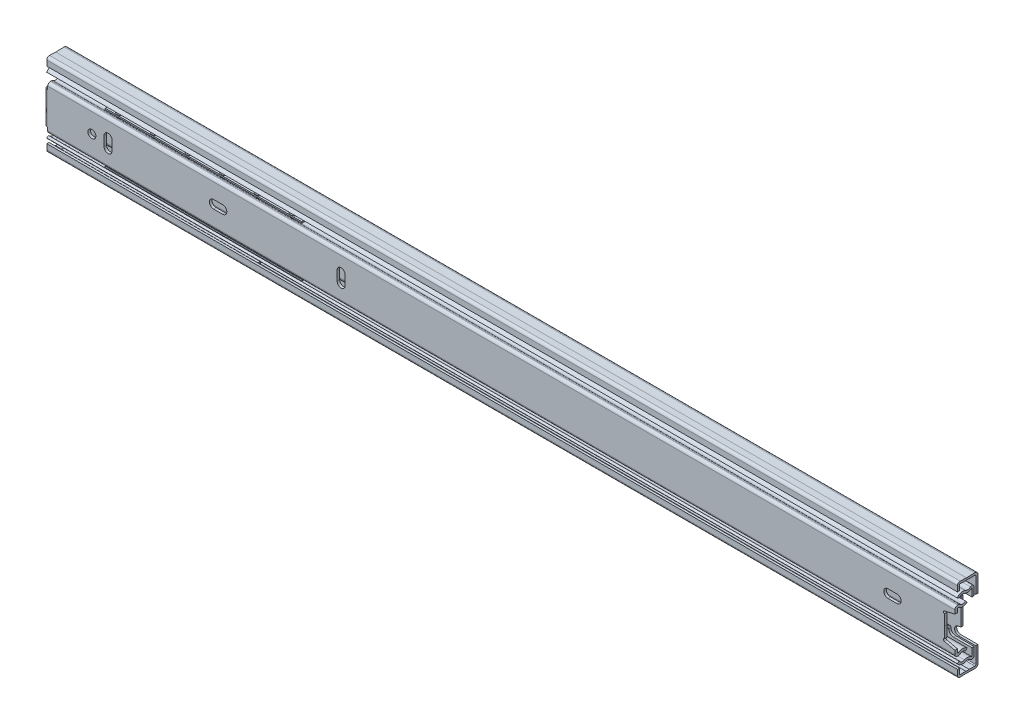
SolidWorks part; units mm, degrees
ref_plane "Front" through (0, 0, 0) normal (0, 0, 1) x (1, 0, 0)
ref_plane "Top" through (0, 0, 0) normal (0, 1, 0) x (1, 0, 0)
ref_plane "Right" through (0, 0, 0) normal (1, 0, 0) x (0, 0, -1)
sketch "Sketch1" plane through (0, 0, 0) normal (1, 0, 0) x (0, 0, -1)
  line L1 (5.6388, 0) -> (-5.6388, 0) construction
  line L4 (-4.1393, 22.8203) -> (-0.7433, 22.6989)
  line L5 (-1.1312, 21.5182) -> (-4.1819, 21.6273)
  line L6 (-4.445, 18.415) -> (-5.6388, 18.415)
  line L7 (-4.445, 21.3734) -> (-4.445, 18.415)
  line L8 (-5.6388, 18.415) -> (-5.6388, 21.3734)
  line L9 (3.9237, 21.6269) -> (0.7619, 21.5441)
  line L10 (5.6388, 0) -> (5.6388, 21.1191)
  line L11 (4.445, 21.1191) -> (4.445, 0)
  line L12 (5.6388, 0) -> (4.445, 0)
  line L13 (-0.7433, 22.6989) -> (3.8925, 22.8203)
  arc A0 (-4.445, 21.3734) -> (-4.1819, 21.6273) centre (-4.191, 21.3734) cw
  arc A1 (-5.6388, 21.3734) -> (-4.1393, 22.8203) centre (-4.191, 21.3734) cw
  arc A3 (3.9237, 21.6269) -> (4.445, 21.1191) centre (3.937, 21.1191) cw
  arc A4 (3.8925, 22.8203) -> (5.6388, 21.1191) centre (3.937, 21.1191) cw
  arc A5 (-1.1312, 21.5182) -> (0.7619, 21.5441) centre (-0.1524, 19.1744) cw
  dimension "D2" = 19.1744
  dimension "D7" = 0.254
  dimension "D8" = 0.508
  dimension "D6" = 2.54
  dimension "D9" = 1.1938
  dimension "D10" = 88.5
  dimension "D1" = 11.2776
  dimension "D3" = 5.7912
  dimension "D4" = 36.83
  dimension "D5" = 1.1938
  dimension "D11" = 87.953
  dimension "D12" = 45.6406
extrude "Extrude1" add sketch "Sketch1" along normal mid plane 500.126
ref_plane "Travel / 2" through (-250.063, 0, 0) normal (-1, 0, 0) x (0, 0, 1)
sketch "Sketch2" plane through (-250.063, 0, 0) normal (-1, 0, 0) x (0, 0, 1)
  line L0 (0.0254, 6.1159) -> (0.0254, 0)
  line L2 (-5.6388, 0) -> (5.6388, 0) construction
  line L3 (5.6388, 21.3734) -> (5.6388, 18.415) construction
  line L7 (-4.445, 21.1191) -> (-4.445, 0) construction
  line L8 (-5.6388, 0) -> (-5.6388, 21.1191) construction
  line L13 (-3.5306, 16.3766) -> (-3.5306, 9.5217)
  line L46 (-2.3867, 7.7262) -> (-0.4146, 6.8065)
  arc A0 (0.0254, 6.1159) -> (-0.4146, 6.8065) centre (-0.7366, 6.1159) ccw
  arc A1 (-1.5056, 17.2916) -> (1.2415, 16.9143) centre (0.1524, 19.1744) ccw
  arc A4 (1.1312, 21.5182) -> (-0.7619, 21.5441) centre (0.1524, 19.1744) ccw construction
  arc A19 (-3.5306, 9.5217) -> (-2.3867, 7.7262) centre (-1.5494, 9.5217) ccw
  arc A25 (-1.5056, 17.2916) -> (-3.5306, 16.3766) centre (-2.3114, 16.3766) ccw
  arc A51 (5.7404, 15.6277) -> (1.2415, 16.9143) centre (2.7686, 13.7451) ccw
  dimension "D2" = 8.4074
  dimension "D3" = 27.4903
  dimension "D6" = 1.9812
  dimension "D8" = 12.2319
  dimension "D10" = 2.5088
  dimension "D11" = 1.2192
  dimension "D4" = 0.762
  dimension "D5" = 4.4704
  dimension "D7" = 115
  dimension "D9" = 19.0435
  dimension "D13" = 11.3792
extrude "Middle Member" add sketch "Sketch2" against normal blind 500.126 separate body thin thin type one direction reverse wall 1.2192
ref_plane "Travel" through (-250.063, 0, 0) normal (-1, 0, 0) x (0, 0, 1)
sketch "Sketch3" plane through (-250.063, 0, 0) normal (-1, 0, 0) x (0, 0, 1)
  line L0 (1.2446, 0) -> (0.0254, 0) construction
  line L1 (-5.6388, 0) -> (-5.6388, 21.1191) construction
  line L56 (7.0612, 0) -> (7.0612, 10.6235)
  line L93 (5.5372, 12.1475) -> (5.1643, 12.1475)
  arc A0 (1.2082, 11.9072) -> (4.2365, 11.8325) centre (2.7686, 13.7451) ccw
  arc A29 (7.0612, 10.6235) -> (5.5372, 12.1475) centre (5.5372, 10.6235) ccw
  arc A53 (5.1643, 12.1475) -> (4.2365, 11.8325) centre (5.1643, 10.6235) ccw
  dimension "D1" = 1.524
  dimension "D4" = 1.524
  dimension "D5" = 2.411
  dimension "D2" = 12.7
  dimension "D3" = 12.1475
  dimension "D6" = 5.853
extrude "Drawer Member" add sketch "Sketch3" against normal blind 500.126 thin thin type one direction wall 1.397
sketch "Sketch6" plane through (0, 0, 7.0612) normal (0, 0, 1) x (1, 0, 0)
  line L1 (-250.063, 0) -> (-248.158, 0)
  line L2 (-250.063, 0) -> (-250.063, 12.1475)
  line L3 (-250.063, 12.1475) -> (-248.158, 12.1475)
  line L4 (-248.158, 0) -> (-248.158, 12.1475)
  line L5 (250.063, 12.1475) -> (-250.063, 12.1475) construction
  line L7 (-250.063, 10.6235) -> (-250.063, 0) construction
  line L8 (250.063, 0) -> (-250.063, 0) construction
  dimension "D1" = 1.905
extrude "Cut-Extrude1" cut sketch "Sketch6" against normal through all
sketch "Sketch7" plane through (0, 0, 0) normal (0, -1, 0) x (1, 0, 0)
  line L0 (-248.158, 7.0612) -> (-248.412, 7.0612)
  line L1 (-250.063, 5.4102) -> (-250.063, 0.3041)
  line L2 (-250.063, 0.3041) -> (-248.666, 0.3041)
  line L3 (-248.666, 0.3041) -> (-248.666, 5.4102)
  line L4 (-248.412, 5.6642) -> (-248.158, 5.6642)
  line L5 (250.063, 5.6642) -> (-248.158, 5.6642) construction
  line L6 (-248.158, 7.0612) -> (-248.158, 5.6642)
  line L7 (250.063, 0.3041) -> (-248.158, 0.3041) construction
  line L9 (-248.158, 5.087) -> (-248.158, 0.3041) construction
  arc A0 (-248.412, 5.6642) -> (-248.666, 5.4102) centre (-248.412, 5.4102) ccw
  arc A1 (-248.412, 7.0612) -> (-250.063, 5.4102) centre (-248.412, 5.4102) ccw
  dimension "D1" = 0.254
  dimension "D2" = 1.905
extrude "Extrude4" add sketch "Sketch7" against normal blind 8.89
sketch "Sketch8" plane through (0, 0, -4.445) normal (0, 0, 1) x (1, 0, 0)
  line L0 (240.4245, 7.6456) -> (241.8588, 7.493)
  line L1 (250.063, 12.2048) -> (240.6664, 12.2048)
  line L2 (241.8588, 7.493) -> (241.8588, 0)
  line L3 (250.063, 0) -> (-250.063, 0) construction
  line L4 (250.063, 21.1191) -> (250.063, 0) construction
  line L5 (250.063, 12.2048) -> (250.063, 0)
  line L6 (250.063, 0) -> (241.8588, 0)
  arc A0 (240.6664, 12.2048) -> (240.4245, 7.6456) centre (240.6664, 9.9188) ccw
  dimension "D3" = 9.9188
  dimension "D1" = 12.2048
  dimension "D2" = 8.2042
  dimension "D4" = 9.3966
  dimension "D5" = 7.493
extrude "Cut-Extrude2" cut sketch "Sketch8" against normal up to next (1.1938 mm away)
sketch "Sketch11" plane through (0, 0, 7.0612) normal (0, 0, 1) x (1, 0, 0)
  line L0 (244.348, 5.9678) -> (244.348, 0)
  line L8 (250.063, 8.5893) -> (244.2037, 7.2212)
  line L11 (244.348, 0) -> (250.063, 0)
  line L12 (250.063, 0) -> (250.063, 8.5893)
  arc A1 (244.2037, 7.2212) -> (244.348, 5.9678) centre (244.3481, 6.6028) ccw
  dimension "D3" = 0.635
  dimension "D1" = 5.715
  dimension "D2" = 8.5893
  dimension "D4" = 5.9678
  dimension "D5" = 103.143
extrude "Cut-Extrude3" cut sketch "Sketch11" against normal up to next (1.397 mm away)
sketch "Sketch12" plane through (0, 0, 1.2446) normal (0, 0, 1) x (1, 0, 0)
  line L0 (250.063, 12.065) -> (239.903, 12.065)
  line L1 (250.063, 16.3766) -> (250.063, 9.5217) construction
  line L2 (237.363, 9.525) -> (237.363, 0)
  line L3 (250.063, 0) -> (-250.063, 0) construction
  line L4 (237.363, 0) -> (250.063, 0)
  line L5 (250.063, 0) -> (250.063, 12.065)
  arc A0 (239.903, 12.065) -> (237.363, 9.525) centre (239.903, 9.525) ccw
  point P11 (237.363, 12.065)
  dimension "D3" = 2.54
  dimension "D1" = 12.7
  dimension "D2" = 12.065
extrude "Cut-Extrude4" cut sketch "Sketch12" against normal through all
sketch "Sketch13" plane through (0, 0, -4.445) normal (0, 0, 1) x (1, 0, 0)
  line L0 (-181.6747, 7.112) -> (-206.5032, 7.112)
  line L1 (241.8588, 0) -> (-250.063, 0) construction
  line L2 (-189.7646, 0) -> (-189.7646, 4.2392) construction
  line L3 (-232.6017, 10.287) -> (-181.6747, 10.287)
  line L4 (-250.063, 21.1191) -> (-250.063, 0) construction
  line L5 (-210.3132, 7.112) -> (-232.6017, 7.112)
  line L6 (-209.5512, 0) -> (-209.5512, 6.35)
  line L7 (-207.2652, 6.35) -> (-207.2652, 0)
  line L8 (-187.2881, 2.286) -> (-192.2411, 2.286)
  line L13 (-226.3406, 0) -> (-221.7686, 0)
  line L14 (-218.238, 0) -> (-211.888, 0)
  line L15 (-209.5512, 0) -> (-207.2652, 0)
  line L16 (-204.7506, 0) -> (-200.1786, 0)
  line L17 (-194.5271, 0) -> (-185.0021, 0)
  arc A1 (-232.6017, 10.287) -> (-232.6017, 7.112) centre (-232.6017, 8.6995) ccw
  arc A2 (-209.5512, 6.35) -> (-210.3132, 7.112) centre (-210.3132, 6.35) ccw
  arc A4 (-206.5032, 7.112) -> (-207.2652, 6.35) centre (-206.5032, 6.35) ccw
  arc A7 (-181.6747, 7.112) -> (-181.6747, 10.287) centre (-181.6747, 8.6995) ccw
  arc A8 (-211.888, 0) -> (-218.238, 0) centre (-215.063, 0) ccw
  arc A9 (-221.7686, 0) -> (-226.3406, 0) centre (-224.0546, 0) ccw
  arc A10 (-200.1786, 0) -> (-204.7506, 0) centre (-202.4646, 0) ccw
  arc A11 (-185.0021, 0) -> (-187.2881, 2.286) centre (-187.2881, 0) ccw
  arc A12 (-192.2411, 2.286) -> (-194.5271, 0) centre (-192.2411, 0) ccw
  dimension "D3" = 2.286
  dimension "D4" = 3.175
  dimension "D7" = 8.9916
  dimension "D8" = 21.59
  dimension "D9" = 34.29
  dimension "D10" = 0.762
  dimension "D11" = 17.5387
  dimension "D12" = 9.525
  dimension "D13" = 5.5118
  dimension "D14" = 35
  dimension "D1" = 3.175
  dimension "D2" = 50.927
  dimension "D5" = 2.286
  dimension "D6" = 10.287
extrude "Cut-Extrude5" cut sketch "Sketch13" against normal up to next (1.1938 mm away)
sketch "Sketch32" plane through (0, 0, -5.6388) normal (0, 0, -1) x (-1, 0, 0)
  line L0 (69.6005, 0) -> (79.1255, 0)
  line L1 (83.888, 0) -> (90.238, 0)
  line L2 (93.7305, 0) -> (103.2555, 0)
  line L3 (106.621, 0) -> (111.193, 0)
  line L4 (-241.8588, 0) -> (185.0021, 0) construction
  line L5 (232.6017, 10.287) -> (181.6747, 10.287) construction
  line L6 (181.6747, 7.112) -> (206.5032, 7.112) construction
  line L7 (98.493, 2.286) -> (98.493, -3.4269) construction
  line L8 (74.363, 2.286) -> (74.363, -3.4269) construction
  line L14 (66.4255, 10.287) -> (109.669, 10.287)
  line L15 (105.097, 7.112) -> (66.4255, 7.112)
  line L17 (111.193, 8.763) -> (111.193, 0)
  line L18 (106.621, 0) -> (106.621, 5.588)
  line L23 (71.8865, 2.286) -> (76.8395, 2.286)
  line L25 (96.0165, 2.286) -> (100.9695, 2.286)
  arc A0 (218.238, 0) -> (211.888, 0) centre (215.063, 0) ccw construction
  arc A13 (111.193, 8.763) -> (109.669, 10.287) centre (109.669, 8.763) ccw
  arc A14 (106.621, 5.588) -> (105.097, 7.112) centre (105.097, 5.588) ccw
  arc A17 (66.4255, 10.287) -> (66.4255, 7.112) centre (66.4255, 8.6995) ccw
  arc A20 (79.1255, 0) -> (76.8395, 2.286) centre (76.8395, 0) ccw
  arc A21 (71.8865, 2.286) -> (69.6005, 0) centre (71.8865, 0) ccw
  arc A22 (90.238, 0) -> (83.888, 0) centre (87.063, 0) ccw
  arc A24 (103.2555, 0) -> (100.9695, 2.286) centre (100.9695, 0) ccw
  arc A25 (96.0165, 2.286) -> (93.7305, 0) centre (96.0165, 0) ccw
  dimension "D2" = 1.524
  dimension "D3" = 3.175
  dimension "D4" = 9.525
  dimension "D5" = 2.286
  dimension "D6" = 11.43
  dimension "D7" = 12.7
  dimension "D8" = 24.13
  dimension "D9" = 20.6375
  dimension "D10" = 128
  dimension "D1" = 4.572
extrude "Cut-Extrude14" cut sketch "Sketch32" against normal up to next (1.1938 mm away)
sketch "Sketch33" plane through (83.6094, 0.8125, -5.6388) normal (0, 0, -1) x (-1, 0, 0)
  line L0 (57.2099, -0.8125) -> (66.7349, -0.8125)
  line L1 (71.4974, -0.8125) -> (77.8474, -0.8125)
  line L2 (81.3399, -0.8125) -> (90.8649, -0.8125)
  line L3 (94.2304, -0.8125) -> (98.8024, -0.8125)
  line L7 (86.1024, 1.4735) -> (86.1024, -4.2394) construction
  line L8 (61.9724, 1.4735) -> (61.9724, -3.4269) construction
  line L9 (-158.2494, -0.8125) -> (153.2099, -0.8125) construction
  line L10 (193.2784, 9.4745) -> (150.0349, 9.4745) construction
  line L11 (150.0349, 6.2995) -> (188.7064, 6.2995) construction
  line L14 (54.0349, 9.4745) -> (97.2784, 9.4745)
  line L15 (92.7064, 6.2995) -> (54.0349, 6.2995)
  line L17 (98.8024, 7.9505) -> (98.8024, -0.8125)
  line L18 (94.2304, -0.8125) -> (94.2304, 4.7755)
  line L23 (59.4959, 1.4735) -> (64.4489, 1.4735)
  line L25 (83.6259, 1.4735) -> (88.5789, 1.4735)
  arc A1 (301.8474, -0.8125) -> (295.4974, -0.8125) centre (298.6724, -0.8125) ccw construction
  arc A13 (98.8024, 7.9505) -> (97.2784, 9.4745) centre (97.2784, 7.9505) ccw
  arc A14 (94.2304, 4.7755) -> (92.7064, 6.2995) centre (92.7064, 4.7755) ccw
  arc A17 (54.0349, 9.4745) -> (54.0349, 6.2995) centre (54.0349, 7.887) ccw
  arc A20 (66.7349, -0.8125) -> (64.4489, 1.4735) centre (64.4489, -0.8125) ccw
  arc A21 (59.4959, 1.4735) -> (57.2099, -0.8125) centre (59.4959, -0.8125) ccw
  arc A22 (77.8474, -0.8125) -> (71.4974, -0.8125) centre (74.6724, -0.8125) ccw
  arc A24 (90.8649, -0.8125) -> (88.5789, 1.4735) centre (88.5789, -0.8125) ccw
  arc A25 (83.6259, 1.4735) -> (81.3399, -0.8125) centre (83.6259, -0.8125) ccw
  dimension "D2" = 1.524
  dimension "D3" = 3.175
  dimension "D4" = 9.525
  dimension "D5" = 2.286
  dimension "D6" = 11.43
  dimension "D7" = 12.7
  dimension "D8" = 24.13
  dimension "D9" = 20.6375
  dimension "D10" = 224
  dimension "D1" = 4.572
extrude "Cut-Extrude6" cut sketch "Sketch33" against normal up to next (1.1938 mm away)
sketch "Sketch34" plane through (169.8236, 1.4527, -5.6388) normal (0, 0, -1) x (-1, 0, 0)
  line L0 (-16.6239, -1.4527) -> (-7.0989, -1.4527)
  line L1 (-2.3364, -1.4527) -> (4.0136, -1.4527)
  line L2 (7.5061, -1.4527) -> (17.0311, -1.4527)
  line L3 (20.3966, -1.4527) -> (24.9686, -1.4527)
  line L4 (-72.0352, -1.4527) -> (143.4241, -1.4527) construction
  line L7 (12.2686, 0.8333) -> (12.2686, -4.8796) construction
  line L8 (-11.8614, 0.8333) -> (-11.8614, -4.0671) construction
  line L9 (279.4926, 8.8343) -> (236.2491, 8.8343) construction
  line L10 (236.2491, 5.6593) -> (274.9206, 5.6593) construction
  line L14 (-19.7989, 8.8343) -> (23.4446, 8.8343)
  line L15 (18.8726, 5.6593) -> (-19.7989, 5.6593)
  line L17 (24.9686, 7.3103) -> (24.9686, -1.4527)
  line L18 (20.3966, -1.4527) -> (20.3966, 4.1353)
  line L23 (-14.3379, 0.8333) -> (-9.3849, 0.8333)
  line L25 (9.7921, 0.8333) -> (14.7451, 0.8333)
  arc A0 (388.0616, -1.4527) -> (381.7116, -1.4527) centre (384.8866, -1.4527) ccw construction
  arc A13 (24.9686, 7.3103) -> (23.4446, 8.8343) centre (23.4446, 7.3103) ccw
  arc A14 (20.3966, 4.1353) -> (18.8726, 5.6593) centre (18.8726, 4.1353) ccw
  arc A17 (-19.7989, 8.8343) -> (-19.7989, 5.6593) centre (-19.7989, 7.2468) ccw
  arc A20 (-7.0989, -1.4527) -> (-9.3849, 0.8333) centre (-9.3849, -1.4527) ccw
  arc A21 (-14.3379, 0.8333) -> (-16.6239, -1.4527) centre (-14.3379, -1.4527) ccw
  arc A22 (4.0136, -1.4527) -> (-2.3364, -1.4527) centre (0.8386, -1.4527) ccw
  arc A24 (17.0311, -1.4527) -> (14.7451, 0.8333) centre (14.7451, -1.4527) ccw
  arc A25 (9.7921, 0.8333) -> (7.5061, -1.4527) centre (9.7921, -1.4527) ccw
  dimension "D2" = 1.524
  dimension "D3" = 3.175
  dimension "D4" = 9.525
  dimension "D5" = 2.286
  dimension "D6" = 11.43
  dimension "D7" = 12.7
  dimension "D8" = 24.13
  dimension "D9" = 20.6375
  dimension "D10" = 384.048
  dimension "D1" = 4.572
extrude "Cut E" cut sketch "Sketch34" against normal up to next (1.1938 mm away)
sketch "Sketch24" plane through (0, 0, 7.0612) normal (0, 0, 1) x (1, 0, 0)
  line L0 (244.348, 0) -> (-248.412, 0) construction
  line L1 (-215.011, 4.826) -> (-215.011, 0) construction
  line L2 (-217.1954, 2.6416) -> (-217.1954, 0)
  line L3 (-217.1954, 0) -> (-212.8266, 0)
  line L4 (-212.8266, 0) -> (-212.8266, 2.6416)
  line L5 (-159.3215, 0) -> (-149.7965, 0)
  line L6 (-157.0355, 2.286) -> (-152.0825, 2.286)
  line L8 (-89.1954, 2.6416) -> (-89.1954, 0)
  line L9 (-89.1954, 0) -> (-84.8266, 0)
  line L10 (-84.8266, 0) -> (-84.8266, 2.6416)
  line L11 (-250.063, 8.89) -> (-250.063, 0) construction
  line L12 (-154.559, 2.286) -> (-154.559, 0) construction
  circle A0 centre (-223.901, 0) radius 2.1844
  arc A1 (-217.1954, 2.6416) -> (-212.8266, 2.6416) centre (-215.011, 2.6416) cw
  arc A2 (-159.3215, 0) -> (-157.0355, 2.286) centre (-157.0355, 0) cw
  arc A3 (-152.0825, 2.286) -> (-149.7965, 0) centre (-152.0825, 0) cw
  arc A4 (-89.1954, 2.6416) -> (-84.8266, 2.6416) centre (-87.011, 2.6416) cw
  dimension "D1" = 4.3688
  dimension "D4" = 8.89
  dimension "D5" = 2.286
  dimension "D7" = 60.452
  dimension "D8" = 128
  dimension "D2" = 35.052
  dimension "D3" = 4.826
  dimension "D6" = 9.525
extrude "Cut-Extrude13" cut sketch "Sketch24" against normal up to next (1.397 mm away)
sketch "Sketch25" plane through (0, 0, 7.0612) normal (0, 0, 1) x (1, 0, 0)
  line L1 (244.348, 0) -> (-84.8266, 0) construction
  line L5 (220.5355, 0) -> (211.0105, 0)
  line L6 (-152.0825, 2.286) -> (-157.0355, 2.286) construction
  line L7 (213.2965, 2.286) -> (218.2495, 2.286)
  line L8 (215.773, 0) -> (215.773, 2.286) construction
  arc A1 (-212.8266, 2.6416) -> (-217.1954, 2.6416) centre (-215.011, 2.6416) ccw construction
  arc A3 (213.2965, 2.286) -> (211.0105, 0) centre (213.2965, 0) ccw
  arc A4 (218.2495, 2.286) -> (220.5355, 0) centre (218.2495, 0) cw
  arc A5 (-149.7965, 0) -> (-152.0825, 2.286) centre (-152.0825, 0) ccw construction
  dimension "D1" = 430.784
extrude "Cut D" cut sketch "Sketch25" against normal up to next (1.397 mm away)
sketch "Sketch36" plane through (0, 0, 7.0612) normal (0, 0, 1) x (1, 0, 0)
  line L0 (198.8046, 0) -> (203.1734, 0)
  line L1 (203.1734, 0) -> (203.1734, 2.6416)
  line L2 (198.8046, 2.6416) -> (198.8046, 0)
  line L4 (211.0105, 0) -> (-84.8266, 0) construction
  line L5 (-212.8266, 0) -> (-212.8266, 2.6416) construction
  arc A0 (203.1734, 2.6416) -> (198.8046, 2.6416) centre (200.989, 2.6416) ccw
  circle A1 centre (188.289, 0) radius 2.1844
  arc A5 (-212.8266, 2.6416) -> (-217.1954, 2.6416) centre (-215.011, 2.6416) ccw construction
  dimension "D1" = 4.3688
  dimension "D2" = 416
  dimension "D3" = 12.7
extrude "Cut B" [suppressed] cut sketch "Sketch36" against normal up to next
sketch "Sketch38" plane through (0, 0, 7.0612) normal (0, 0, 1) x (1, 0, 0)
  line L0 (6.8046, 0) -> (6.8046, 2.6416)
  line L1 (211.0105, 0) -> (-84.8266, 0) construction
  line L2 (11.1734, 2.6416) -> (11.1734, 0)
  line L3 (11.1734, 0) -> (6.8046, 0)
  line L4 (-212.8266, 0) -> (-212.8266, 2.6416) construction
  line L5 (15.72, 0) -> (23.594, 0)
  line L6 (15.72, 0) -> (15.72, 2.3749)
  line L7 (15.72, 2.3749) -> (23.594, 2.3749)
  line L8 (23.594, 0) -> (23.594, 2.3749)
  line L9 (8.989, 7.182) -> (8.989, -4.0911) construction
  line L10 (2.258, 0) -> (-5.616, 0)
  line L11 (2.258, 0) -> (2.258, 2.3749)
  line L12 (2.258, 2.3749) -> (-5.616, 2.3749)
  line L13 (-5.616, 0) -> (-5.616, 2.3749)
  line L14 (19.657, 2.3749) -> (19.657, -3.2385) construction
  arc A0 (6.8046, 2.6416) -> (11.1734, 2.6416) centre (8.989, 2.6416) cw
  arc A1 (-212.8266, 2.6416) -> (-217.1954, 2.6416) centre (-215.011, 2.6416) ccw construction
  dimension "D4" = 224
  dimension "D1" = 7.874
  dimension "D2" = 2.3749
  dimension "D3" = 10.668
extrude "Cut A" [suppressed] cut sketch "Sketch38" against normal up to next
ref_plane "Plane3" through (-237.363, 0, 0) normal (-1, 0, 0) x (0, 0, 1)
sketch "Sketch27" plane through (-237.363, 0, 0) normal (-1, 0, 0) x (0, 0, 1)
  line L0 (0.1524, 21.6832) -> (0.1524, 16.6656)
  line L1 (0.1524, 23.635) -> (0.1524, 15.2838) construction
  arc A0 (0.1524, 16.6656) -> (0.1524, 21.6832) centre (0.1524, 19.1744) ccw
  arc A1 (-1.5056, 17.2916) -> (1.2415, 16.9143) centre (0.1524, 19.1744) ccw construction
revolve "Revolve1" add sketch "Sketch27" angle 360 about L1
pattern_linear "LPattern1" count 6 spacing 19.05 along (1, 0, 0) of bodies 128
sketch "Sketch28" plane through (-237.363, 0, 0) normal (-1, 0, 0) x (0, 0, 1)
  line L0 (2.6612, 19.1744) -> (-2.3564, 19.1744) construction
  line L1 (3.9624, 18.7934) -> (-3.6576, 18.7934)
  line L2 (3.9624, 18.7934) -> (3.9624, 19.5554)
  line L3 (3.9624, 19.5554) -> (-3.6576, 19.5554)
  line L4 (-3.6576, 18.7934) -> (-3.6576, 19.5554)
  line L5 (0.1524, 20.5465) -> (0.1524, 17.804) construction
  circle A1 centre (0.1524, 19.1744) radius 2.5088 construction
  point P8 (0.1524, 19.1744)
  dimension "D1" = 7.62
  dimension "D2" = 0.762
extrude "Extrude7" add sketch "Sketch28" along normal blind 6.35 and the other way blind 101.6
ref_plane "Plane4" through (-211.963, 0, 0) normal (-1, 0, 0) x (0, 0, 1)
sketch "Sketch29" plane through (-211.963, 0, 0) normal (-1, 0, 0) x (0, 0, 1)
  line L0 (2.7686, 16.0438) -> (2.7686, 11.4464)
  line L1 (2.7686, 16.6801) -> (2.7686, 10.2973) construction
  arc A0 (2.7686, 11.4464) -> (2.7686, 16.0438) centre (2.7686, 13.7451) ccw
  arc A1 (4.7105, 14.9753) -> (1.7707, 15.816) centre (2.7686, 13.7451) ccw construction
revolve "Revolve2" add sketch "Sketch29" angle 360 about L1
pattern_linear "LPattern2" count 6 spacing 19.05 along (1, 0, 0) of bodies 135
sketch "Sketch30" plane through (-211.963, 0, 0) normal (-1, 0, 0) x (0, 0, 1)
  line L0 (0.4699, 13.7451) -> (5.0673, 13.7451) construction
  line L1 (3.9624, 18.7934) -> (3.9624, 19.5554) construction
  line L2 (0.2286, 14.1261) -> (5.3086, 14.1261)
  line L3 (0.2286, 14.1261) -> (0.2286, 13.3641)
  line L4 (0.2286, 13.3641) -> (5.3086, 13.3641)
  line L5 (5.3086, 14.1261) -> (5.3086, 13.3641)
  line L7 (2.7686, 14.2437) -> (2.7686, 12.7853) construction
  circle A0 centre (2.7686, 13.7451) radius 2.2987 construction
  point P4 (2.7686, 13.7451)
  dimension "D1" = 5.08
extrude "Extrude8" add sketch "Sketch30" along normal blind 6.35 and the other way blind 101.6
mirror "Mirror3" about plane through (0, 0, 0) normal (0, 1, 0) of bodies 126 119 164 117 124 127 159
mirror "Mirror5" about plane through (0, 0, 0) normal (0, 1, 0) of bodies 141 134
